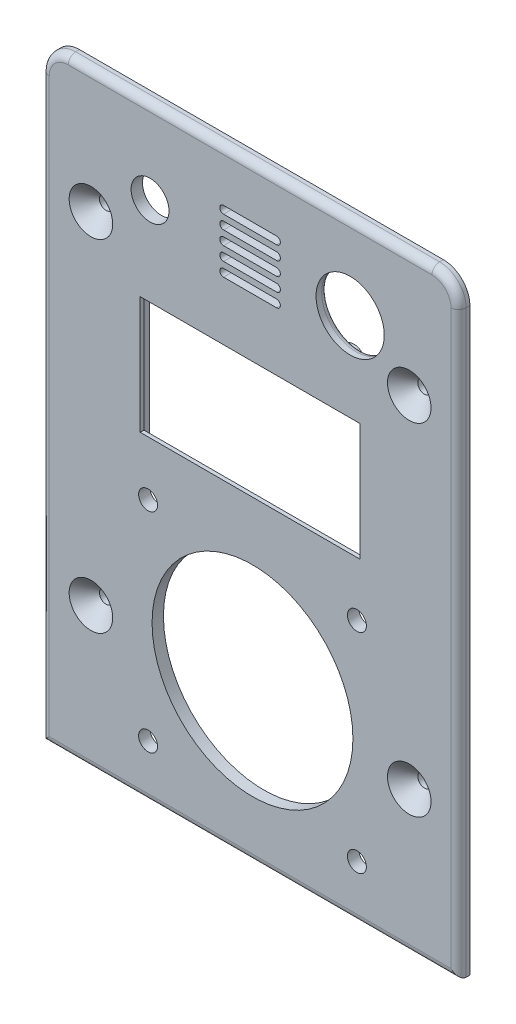
SolidWorks part; units mm, degrees
ref_plane "Front Plane" through (0, 0, 0) normal (0, 0, 1) x (1, 0, 0)
ref_plane "Top Plane" through (0, 0, 0) normal (0, 1, 0) x (1, 0, 0)
ref_plane "Right Plane" through (0, 0, 0) normal (1, 0, 0) x (0, 0, -1)
sketch "Sketch1" plane through (0, 0, 0) normal (0, 0, 1) x (1, 0, 0)
  line L1 (0, 0) -> (110, 0)
  line L2 (0, 0) -> (0, 153)
  line L3 (7, 160) -> (103, 160)
  line L4 (110, 0) -> (110, 153)
  arc A0 (103, 160) -> (110, 153) centre (103, 153) cw
  arc A1 (0, 153) -> (7, 160) centre (7, 153) cw
  point P7 (110, 160)
  point P10 (0, 160)
  dimension "D3" = 7
  dimension "D1" = 110
  dimension "D2" = 160
extrude "Boss-Extrude1" add sketch "Sketch1" along normal blind 3
fillet "Fillet1" radius 2 6 edges at (2.0503, 157.9497, 3) (55, 160, 3) (107.9497, 157.9497, 3) (110, 76.5, 3) (55, 0, 3) (0, 76.5, 3)
sketch "Sketch3" plane through (0, 0, 0) normal (0, 0, -1) x (-1, 0, 0)
  line L0 (0, 0) -> (-110, 0) construction
  line L1 (-103, 0) -> (-7, 0)
  line L2 (-103, 0) -> (-103, 152.5)
  line L3 (-103, 152.5) -> (-7, 152.5)
  line L4 (-7, 0) -> (-7, 152.5)
  line L5 (-101.4, 1.6) -> (-101.4, 33.5)
  line L6 (-101.4, 150.9) -> (-8.6, 150.9)
  line L7 (-8.6, 1.6) -> (-8.6, 33.5)
  line L8 (-101.4, 1.6) -> (-8.6, 1.6)
  line L9 (-97, 131.5) -> (-101.4, 131.5)
  line L10 (-97, 123.5) -> (-101.4, 123.5)
  line L11 (-13, 131.5) -> (-8.6, 131.5)
  line L12 (-8.6, 123.5) -> (-13, 123.5)
  line L13 (-13, 33.5) -> (-8.6, 33.5)
  line L14 (-13, 41.5) -> (-8.6, 41.5)
  line L15 (-97, 41.5) -> (-101.4, 41.5)
  line L16 (-101.4, 33.5) -> (-97, 33.5)
  line L17 (-101.4, 41.5) -> (-101.4, 123.5)
  line L18 (-8.6, 41.5) -> (-8.6, 123.5)
  line L19 (-101.4, 1.6) -> (-101.4, 150.9) construction
  line L20 (-8.6, 131.5) -> (-8.6, 150.9)
  line L21 (-8.6, 1.6) -> (-8.6, 150.9) construction
  line L22 (-101.4, 131.5) -> (-101.4, 150.9)
  arc A0 (-97, 123.5) -> (-97, 131.5) centre (-97, 127.5) ccw
  arc A1 (-13, 131.5) -> (-13, 123.5) centre (-13, 127.5) ccw
  arc A2 (-97, 33.5) -> (-97, 41.5) centre (-97, 37.5) ccw
  arc A3 (-13, 41.5) -> (-13, 33.5) centre (-13, 37.5) ccw
  point P6 (-55, 0)
  point P7 (-55, 0)
  dimension "D4" = 8
  dimension "D5" = 6
  dimension "D6" = 6
  dimension "D8" = 90
  dimension "D1" = 96
  dimension "D2" = 152.5
  dimension "D7" = 25
  dimension "D3" = 1.6
extrude "Boss-Extrude2" add sketch "Sketch3" along normal blind 3.9
sketch "Sketch4" plane through (0, 0, -3.9) normal (0, 0, -1) x (-1, 0, 0)
  circle A0 centre (-97, 127.5) radius 1.75
  circle A1 centre (-13, 127.5) radius 1.75
  circle A2 centre (-13, 37.5) radius 1.75
  circle A3 centre (-97, 37.5) radius 1.75
  dimension "D1" = 3.5
extrude "Cut-Extrude1" cut sketch "Sketch4" against normal up to next
chamfer "Chamfer1" distance 4 angle 45 4 edges at (95.25, 37.5, 3) (11.25, 37.5, 3) (11.25, 127.5, 3) (95.25, 127.5, 3)
sketch "Sketch5" plane through (0, 0, 0) normal (0, 0, -1) x (-1, 0, 0)
  line L0 (-8.6, 150.9) -> (-101.4, 150.9) construction
  line L1 (-8.6, 131.5) -> (-8.6, 150.9) construction
  line L2 (-101.4, 150.9) -> (-101.4, 131.5) construction
  circle A0 centre (-28.6, 137.9) radius 5
  circle A1 centre (-81.4, 137.9) radius 9
  dimension "D1" = 13
  dimension "D2" = 20
  dimension "D3" = 10
  dimension "D4" = 18
  dimension "D5" = 20
extrude "Cut-Extrude2" cut sketch "Sketch5" against normal through all
fillet "Fillet2" radius 1.5 1 edges at (72.4, 137.9, 0)
sketch "Sketch7" plane through (0, 0, 0) normal (0, 0, -1) x (-1, 0, 0)
  line L0 (-8.6, 150.9) -> (-101.4, 150.9) construction
  line L1 (-65, 147.9) -> (-45, 147.9)
  line L2 (-65, 147.9) -> (-65, 127.9)
  line L3 (-65, 127.9) -> (-45, 127.9)
  line L4 (-45, 147.9) -> (-45, 127.9)
  line L5 (-64, 146.9) -> (-46, 146.9)
  line L6 (-46, 146.9) -> (-46, 128.9)
  line L7 (-64, 128.9) -> (-46, 128.9)
  line L8 (-64, 146.9) -> (-64, 128.9)
  point P6 (-55, 150.9)
  point P7 (-55, 147.9)
  dimension "D1" = 20
  dimension "D2" = 20
  dimension "D3" = 3
  dimension "D4" = 1
extrude "Boss-Extrude3" add sketch "Sketch7" along normal up to surface (3.9 mm away) up to face at (95.25, 37.5, -3.9)
sketch "Sketch8" plane through (0, 0, 0) normal (0, 0, -1) x (-1, 0, 0)
  line L0 (-62, 145.4) -> (-48, 145.4) construction
  line L1 (-62, 146.4) -> (-48, 146.4)
  line L2 (-62, 144.4) -> (-48, 144.4)
  line L3 (-46, 146.9) -> (-64, 146.9) construction
  line L4 (-62, 141.8) -> (-48, 141.8) construction
  line L5 (-62, 142.8) -> (-48, 142.8)
  line L6 (-62, 140.8) -> (-48, 140.8)
  line L7 (-62, 138.2) -> (-48, 138.2) construction
  line L8 (-62, 139.2) -> (-48, 139.2)
  line L9 (-62, 137.2) -> (-48, 137.2)
  line L10 (-62, 134.6) -> (-48, 134.6) construction
  line L11 (-62, 135.6) -> (-48, 135.6)
  line L12 (-62, 133.6) -> (-48, 133.6)
  line L13 (-62, 131) -> (-48, 131) construction
  line L14 (-62, 132) -> (-48, 132)
  line L15 (-62, 130) -> (-48, 130)
  arc A0 (-62, 146.4) -> (-62, 144.4) centre (-62, 145.4) ccw
  arc A1 (-48, 144.4) -> (-48, 146.4) centre (-48, 145.4) ccw
  arc A2 (-62, 142.8) -> (-62, 140.8) centre (-62, 141.8) ccw
  arc A3 (-48, 140.8) -> (-48, 142.8) centre (-48, 141.8) ccw
  arc A4 (-62, 139.2) -> (-62, 137.2) centre (-62, 138.2) ccw
  arc A5 (-48, 137.2) -> (-48, 139.2) centre (-48, 138.2) ccw
  arc A6 (-62, 135.6) -> (-62, 133.6) centre (-62, 134.6) ccw
  arc A7 (-48, 133.6) -> (-48, 135.6) centre (-48, 134.6) ccw
  arc A8 (-62, 132) -> (-62, 130) centre (-62, 131) ccw
  arc A9 (-48, 130) -> (-48, 132) centre (-48, 131) ccw
  point P2 (-55, 145.4)
  point P9 (-55, 146.9)
  point P14 (-55, 141.8)
  point P21 (-55, 138.2)
  point P28 (-55, 134.6)
  point P35 (-55, 131)
  dimension "D2" = 1
  dimension "D1" = 14
  dimension "D3" = 1.5
  dimension "D4" = 5
extrude "Cut-Extrude3" cut sketch "Sketch8" against normal through all
sketch "Croquis1" plane through (0, 0, 0) normal (0, 0, -1) x (-1, 0, 0)
  circle A0 centre (-28.6, 116.15) radius 1.25
  circle A1 centre (-28.6, 116.15) radius 3
  circle A3 centre (-28.6, 116.15) radius 1.5 construction
  dimension "D1" = 2.5
  dimension "D2" = 6
extrude "Saliente-Extruir1" add sketch "Croquis1" along normal blind 5
sketch "Croquis2" plane through (0, 0, 0) normal (0, 0, -1) x (-1, 0, 0)
  line L0 (-8.6, 150.9) -> (-101.4, 150.9) construction
  line L1 (-92.4, 150.9) -> (-70.4, 150.9)
  line L2 (-92.4, 150.9) -> (-92.4, 147.9)
  line L3 (-92.4, 147.9) -> (-70.4, 147.9)
  line L4 (-70.4, 150.9) -> (-70.4, 147.9)
  line L5 (-91.4, 149.9) -> (-71.4, 149.9) construction
  circle A0 centre (-88.9, 120.4) radius 1.25
  circle A1 centre (-88.9, 120.4) radius 3
  circle A2 centre (-73.9, 120.4) radius 1.25
  circle A3 centre (-73.9, 120.4) radius 3
  point P16 (-81.4, 149.9)
  point P17 (-81.4, 147.9)
  dimension "D1" = 6
  dimension "D2" = 2.5
  dimension "D3" = 3
  dimension "D4" = 22
extrude "Saliente-Extruir2" add sketch "Croquis2" along normal blind 5.5
sketch "Croquis3" plane through (0, 0, 0) normal (0, 0, -1) x (-1, 0, 0)
  line L0 (-101.4, 1.6) -> (-8.6, 1.6) construction
  circle A0 centre (-55.6315, 41.6) radius 26.5
  dimension "D1" = 53
  dimension "45" = 40
extrude "Cortar-Extruir1" cut sketch "Croquis3" against normal up to next
sketch "Croquis4" plane through (0, 0, 0) normal (0, 0, -1) x (-1, 0, 0)
  line L1 (-88.1315, 9.1) -> (-23.1315, 9.1) construction
  line L2 (-88.1315, 9.1) -> (-88.1315, 74.1) construction
  line L3 (-88.1315, 74.1) -> (-23.1315, 74.1) construction
  line L4 (-23.1315, 9.1) -> (-23.1315, 74.1) construction
  line L5 (-88.1315, 9.1) -> (-23.1315, 74.1) construction
  line L6 (-88.1315, 74.1) -> (-23.1315, 9.1) construction
  circle A0 centre (-83.1818, 69.1503) radius 2.5
  circle A1 centre (-28.0813, 69.1503) radius 2.5
  circle A2 centre (-28.0813, 14.0497) radius 2.5
  circle A3 centre (-83.1818, 14.0497) radius 2.5
  point P0 (-55.6315, 41.6)
  dimension "D2" = 5
  dimension "D1" = 65
  dimension "D3" = 7
extrude "Cortar-Extruir2" cut sketch "Croquis4" against normal up to next
sketch "Croquis5" plane through (0, 0, 0) normal (0, 0, -1) x (-1, 0, 0)
  line L0 (-101.4, 95.543) -> (-8.6, 95.543) construction
  line L1 (-101.4, 123.5) -> (-101.4, 41.5) construction
  line L2 (-8.6, 41.5) -> (-8.6, 123.5) construction
  line L4 (-84.5, 75.543) -> (-25.5, 75.543)
  line L5 (-84.5, 75.543) -> (-84.5, 115.543)
  line L6 (-84.5, 115.543) -> (-25.5, 115.543)
  line L7 (-25.5, 75.543) -> (-25.5, 115.543)
  line L8 (-84.5, 75.543) -> (-25.5, 115.543) construction
  line L9 (-84.5, 115.543) -> (-25.5, 75.543) construction
  point P6 (-55, 95.543)
  dimension "D1" = 40
  dimension "D2" = 59
extrude "Cortar-Extruir3" cut sketch "Croquis5" against normal blind 2
sketch "Croquis6" plane through (0, 0, 2) normal (0, 0, -1) x (-1, 0, 0)
  line L0 (-84.5, 115.543) -> (-84.5, 75.543) construction
  line L1 (-84, 114.543) -> (-26, 114.543)
  line L2 (-84.5, 114.543) -> (-84.5, 83.543) construction
  line L3 (-84, 83.543) -> (-26, 83.543)
  line L4 (-25.5, 114.543) -> (-25.5, 83.543) construction
  line L5 (-25.5, 75.543) -> (-25.5, 115.543) construction
  line L6 (-25.5, 115.543) -> (-84.5, 115.543) construction
  line L7 (-26, 114.543) -> (-26, 83.543)
  line L8 (-84, 114.543) -> (-84, 83.543)
  dimension "D1" = 31
  dimension "D2" = 1
  dimension "D3" = 0.5
  dimension "D4" = 0.5
extrude "Cortar-Extruir4" cut sketch "Croquis6" against normal blind 2
